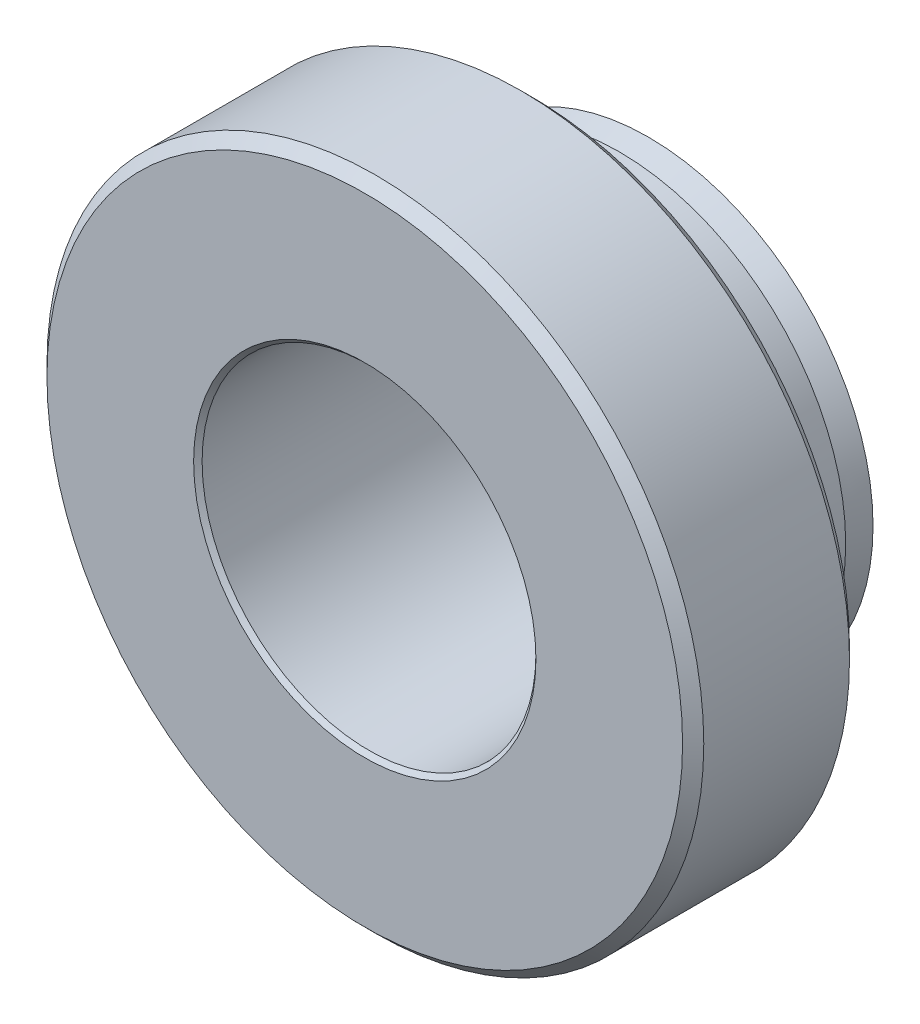
SolidWorks part; units mm, degrees
ref_plane "Front Plane" through (0, 0, 0) normal (0, 0, 1) x (1, 0, 0)
ref_plane "Top Plane" through (0, 0, 0) normal (0, 1, 0) x (1, 0, 0)
ref_plane "Right Plane" through (0, 0, 0) normal (1, 0, 0) x (0, 0, -1)
sketch "Sketch1" plane through (0, 0, 0) normal (0, 0, 1) x (1, 0, 0)
  circle A0 centre (0, 0) radius 3.935
  dimension "A" = 7.87
extrude "Extrude1" add sketch "Sketch1" against normal blind 2
sketch "Sketch15" plane through (0, 0, -2) normal (0, 0, -1) x (-1, 0, 0)
  circle A0 centre (0, 0) radius 2.7
  dimension "hole dia" = 5.4
sketch "Sketch2" plane through (0, 0, -2) normal (0, 0, -1) x (-1, 0, 0)
  circle A0 centre (0, 0) radius 2.7125
  dimension "D1" = 5.425
extrude "Extrude2" add sketch "Sketch2" along normal blind 1.4
sketch "Sketch3" plane through (0, 0, -3.4) normal (0, 0, -1) x (-1, 0, 0)
  line L0 (0, 2.522) -> (0, 3.935)
  circle A1 centre (0, 0) radius 3.935 construction
  circle A2 centre (0, 0) radius 2.522
  circle A3 centre (0, 0) radius 2.522 construction
  dimension "D1" = 0.1905
sketch "Sketch5" plane through (0, 0, -3.4) normal (0, 0, -1) x (-1, 0, 0)
  circle A0 centre (0, 0) radius 3.935 construction
  circle A3 centre (0, 0) radius 2.69
  dimension "C" = 5.38
extrude "Cut-Extrude1" cut sketch "Sketch5" against normal blind 0.35 draft 20 flip side to cut draft outward yes
chamfer "Chamfer2" distance 0.127 angle 45 2 edges at (3.935, 0, 0) (3.935, 0, -2)
sketch "Sketch7" plane through (0, 0, 0) normal (0, 0, 1) x (1, 0, 0)
  circle A0 centre (0, 0) radius 2
  dimension "Thread Od" = 4
extrude "Cut-Extrude3" cut sketch "Sketch7" against normal through all
sketch "Sketch8" plane through (0, 0, -3.4) normal (0, 0, -1) x (-1, 0, 0)
  circle A0 centre (0, 0) radius 2 construction
  circle A1 centre (0, 0) radius 2
curve "Helix/Spiral1" [suppressed] pitch 0.7 height 5.4 turns 7.7143 parameters "pitch"=0.7
sketch "Sketch9" plane through (0, 0, 0) normal (1, 0, 0) x (0, 0, -1)
  line L0 (4.0125, 2) -> (3.75, 1.5453)
  line L1 (3.75, 1.5453) -> (3.6625, 1.5453)
  line L2 (3.6625, 1.5453) -> (3.4, 2)
  line L3 (4.0125, 2) -> (3.4, 2)
  line L4 (3.7062, 2) -> (3.7062, 1.5453) construction
  line L5 (3.8813, 1.7727) -> (3.5312, 1.7727) construction
  line L6 (3.4, -2) -> (3.4, 2) construction
  dimension "D1" = 60
  dimension "D2" = 0.0875
  dimension "D3" = 0.35
sweep "Sweep1" [suppressed] add profiles "Sketch9" path "Helix/Spiral1"
sketch "Sketch10" plane through (0, 0, 0) normal (0, 0, 1) x (1, 0, 0)
  circle A0 centre (0, 0) radius 3.935 construction
  circle A1 centre (0, 0) radius 3.935
extrude "Cut-Extrude4" [suppressed] cut sketch "Sketch10" along normal through all
sketch "Sketch11" plane through (0, 0, -3.4) normal (0, 0, -1) x (-1, 0, 0)
  circle A1 centre (0, 0) radius 2.69 construction
  circle A2 centre (0, 0) radius 2.69
extrude "Cut-Extrude5" [suppressed] cut sketch "Sketch11" along normal through all
sketch "Sketch13" plane through (0, 0, 0) normal (0, 0, 1) x (1, 0, 0)
  circle A2 centre (0, 0) radius 2.0508
  circle A3 centre (0, 0) radius 2.0508
  dimension "D1" = 0.0508
extrude "Cut-Extrude6" cut sketch "Sketch13" against normal through all draft 45
sketch "Sketch14" plane through (0, 0, -3.4) normal (0, 0, -1) x (-1, 0, 0)
  circle A2 centre (0, 0) radius 2.0635
  circle A3 centre (0, 0) radius 2.0635
  dimension "D1" = 0.0635
extrude "Cut-Extrude7" cut sketch "Sketch14" against normal through all draft 45
sketch "Sketch17" plane through (0, 0, 0) normal (1, 0, 0) x (0, 0, -1)
  line L0 (0, 0) -> (3.4, 0) construction
  line L1 (0, 3.808) -> (0, -3.808) construction
  line L2 (3.4, -2.69) -> (3.4, 2.69) construction
  dimension "D1" = 3.4
sketch "Sketch16" plane through (0, 0, -2) normal (0, 0, -1) x (-1, 0, 0)
  line L0 (0, 2.69) -> (0, 3.808) construction
  line L1 (0, 3.249) -> (-0.6028, 2.6447)
  line L2 (0, 3.249) -> (0.6028, 2.6447)
  circle A0 centre (0, 0) radius 2.5626 construction
  circle A1 centre (0, 0) radius 2.69 construction
  circle A2 centre (0, 0) radius 3.808 construction
  circle A3 centre (0, 0) radius 2.7125 construction
  arc A4 (-0.6028, 2.6447) -> (0.6028, 2.6447) centre (0, 0) cw
  circle A5 centre (0, 0) radius 2.7125 construction
  point P2 (0, 3.249)
  dimension "D2" = 1.2056
extrude "Boss-Extrude1" add sketch "Sketch16" along normal blind 0.34
pattern_circular "CirPattern4" count 30 over 360 about axis through (0, 0, -3.4) along (0, 0, -1) of "Boss-Extrude1"
equation "\"D3@Helix/Spiral1\"=\"B@Extrude1\"+\"panel min.@Extrude2\"+2"
equation "\"D2@Sketch9\" = \"pitch@Helix/Spiral1\"*.125"
equation "\"D3@Sketch9\" = \"pitch@Helix/Spiral1\"*.50"
equation "\"D1@Sketch2\" = \"hole dia@Sketch15\"+.025"
equation "\"D1@Cut-Extrude1\" = \"panel min.@Extrude2\"*.25"
equation "\"D2@Sketch16\"=\"D1@Sketch2\"/4.5"
equation "\"D1@CirPattern4\"=360/12"
equation "\"D1@Boss-Extrude1\"=\"D1@Sketch17\"*.1"
